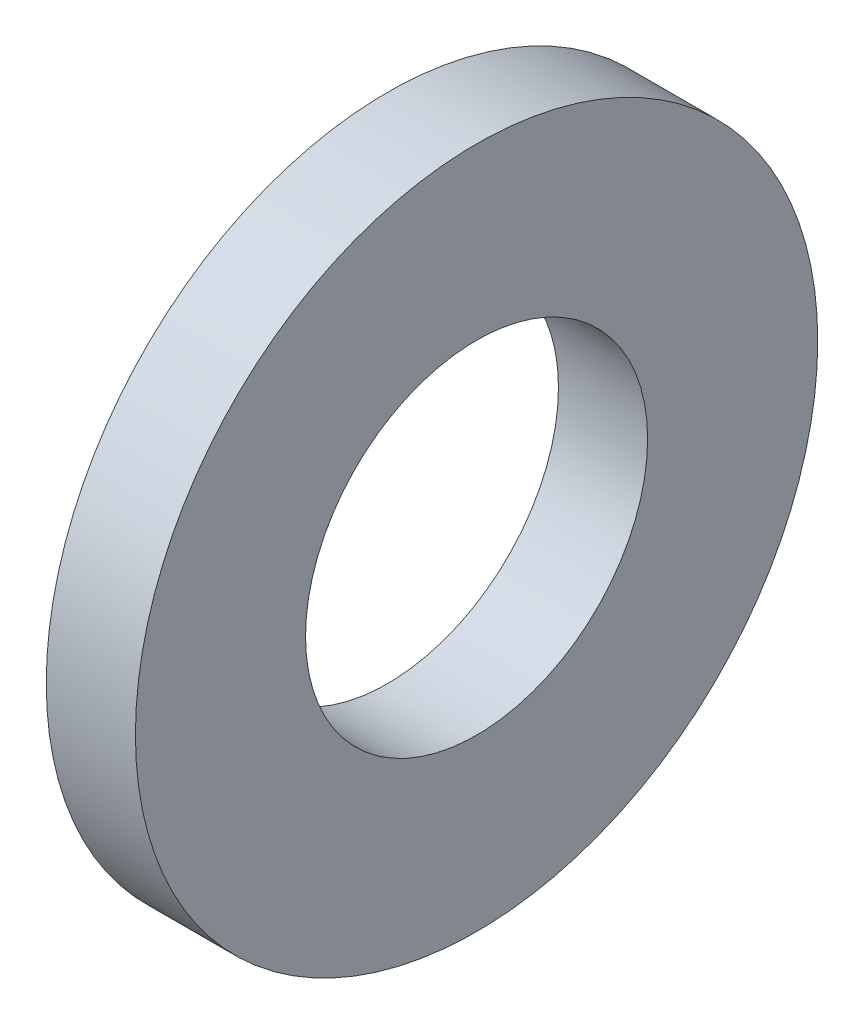
SolidWorks part; units mm, degrees
material "Chrome Stainless Steel"
ref_plane "Front Plane" through (0, 0, 0) normal (0, 0, 1) x (1, 0, 0)
ref_plane "Top Plane" through (0, 0, 0) normal (0, 1, 0) x (1, 0, 0)
ref_plane "Right Plane" through (0, 0, 0) normal (1, 0, 0) x (0, 0, -1)
ref_plane "Plane1" through (0, 0, 0) normal (0, 0, -1) x (-1, 0, 0)
sketch "Sketch1" plane through (0, 0, 0) normal (0, 0, -1) x (-1, 0, 0)
  line L0 (1.2446, 4.7625) -> (0, 4.7625)
  line L1 (0, 4.7625) -> (0, 2.3876)
  line L2 (0, 2.3876) -> (1.2446, 2.3876)
  line L3 (1.2446, 2.3876) -> (1.2446, 4.7625)
  line L4 (0, 0) -> (1.2446, 0) construction
revolve "Revolve1" add sketch "Sketch1" angle 360 about L4 reverse direction yes
